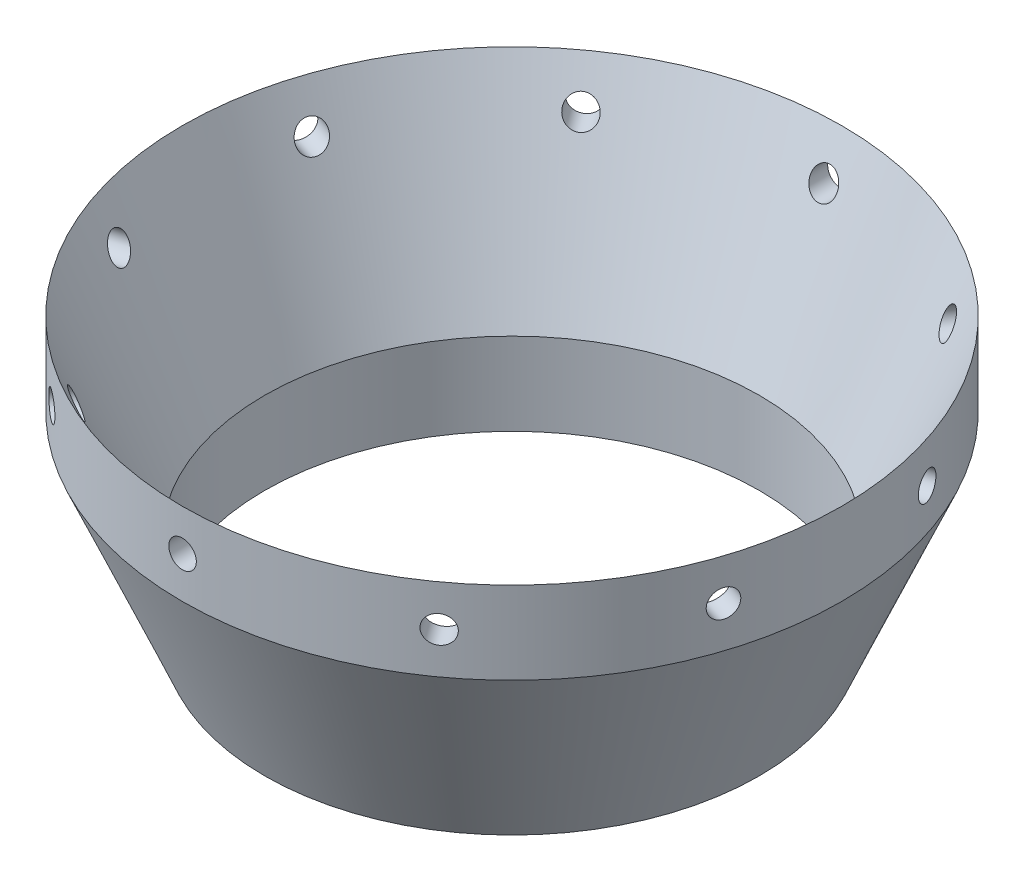
SolidWorks part; units mm, degrees
material "2024-T3"
ref_plane "Front Plane" through (0, 0, 0) normal (0, 0, 1) x (1, 0, 0)
ref_plane "Top Plane" through (0, 0, 0) normal (0, 1, 0) x (1, 0, 0)
ref_plane "Right Plane" through (0, 0, 0) normal (1, 0, 0) x (0, 0, -1)
sketch "Sketch1" plane through (0, 0, 0) normal (0, 0, 1) x (1, 0, 0)
  line L0 (0, 0) -> (0, 220.7687) construction
  line L1 (-57.15, 180.256) -> (-57.15, 199.306)
  line L2 (-57.15, 199.306) -> (-76.2, 243.756)
  line L3 (-76.2, 243.756) -> (-76.2, 224.706)
  line L4 (-76.2, 224.706) -> (-57.15, 180.256)
  dimension "D1" = 57.15
  dimension "D2" = 76.2
  dimension "D3" = 44.45
  dimension "D4" = 19.05
  dimension "D5" = 19.05
revolve "Revolve1" add sketch "Sketch1" angle 360 about L0
sketch "Sketch2" plane through (0, 0, 0) normal (0, 0, 1) x (1, 0, 0)
  line L0 (0, 235.8035) -> (0, 187.481) construction
  line L1 (76.2, 224.706) -> (-76.2, 224.706) construction
  circle A0 centre (0, 234.231) radius 3.175
  dimension "D1" = 9.525
extrude "Cut-Extrude1" cut sketch "Sketch2" against normal through all
ref_axis "Axis1" through (0, 235.8035, 0) along (0, -1, 0)
pattern_circular "CirPattern1" count 10 over 360 about axis through (0, 235.8035, 0) along (0, -1, 0) of "Cut-Extrude1"
